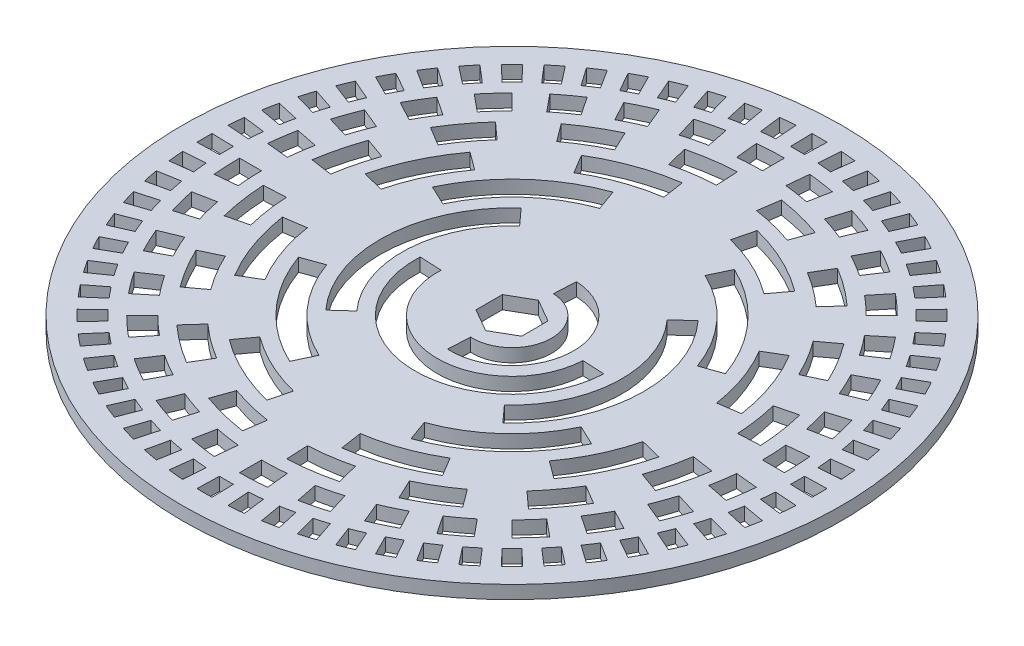
SolidWorks part; units mm, degrees
ref_plane "Front Plane" through (0, 0, 0) normal (0, 0, 1) x (1, 0, 0)
ref_plane "Top Plane" through (0, 0, 0) normal (0, 1, 0) x (1, 0, 0)
ref_plane "Right Plane" through (0, 0, 0) normal (1, 0, 0) x (0, 0, -1)
sketch "Sketch1" plane through (0, 0, 0) normal (0, 1, 0) x (1, 0, 0)
  circle A0 centre (0, 0) radius 75
  dimension "D1" = 150
extrude "Boss-Extrude1" add sketch "Sketch1" along normal blind 3
sketch "Sketch2" plane through (0, 3, 0) normal (0, 1, 0) x (1, 0, 0)
  line L0 (0, 0) -> (0, 75) construction
  line L1 (0, 0) -> (1.8406, 74.9774) construction
  line L2 (0, 0) -> (-1.8406, 74.9774) construction
  line L3 (1.7179, 69.9789) -> (1.5952, 64.9804)
  line L4 (-1.7179, 69.9789) -> (-1.5952, 64.9804)
  circle A0 centre (0, 0) radius 75 construction
  arc A1 (-1.5952, 64.9804) -> (1.5952, 64.9804) centre (0, 0) cw
  arc A2 (1.7179, 69.9789) -> (-1.7179, 69.9789) centre (0, 0) ccw
  dimension "D4" = 5
  dimension "D1" = 2.813
  dimension "D2" = 1.406
  dimension "D3" = 5
extrude "Cut-Extrude1" cut sketch "Sketch2" against normal through all
ref_axis "Axis1" through (0, 3, 0) along (0, -1, 0)
pattern_circular "CirPattern1" count 64 over 360 about axis through (0, 3, 0) along (0, -1, 0) of "Cut-Extrude1"
sketch "Sketch3" plane through (0, 3, 0) normal (0, 1, 0) x (1, 0, 0)
  line L0 (0, 0) -> (-3.6801, 74.9097) construction
  line L1 (0, 0) -> (0, 75) construction
  line L2 (0, 0) -> (-7.3513, 74.6389) construction
  line L3 (0, 0) -> (0, 75) construction
  line L4 (0, 62) -> (0, 57)
  line L5 (-5.587, 56.7255) -> (-6.0771, 61.7015)
  circle A0 centre (0, 0) radius 75 construction
  arc A1 (-6.0771, 61.7015) -> (0, 62) centre (0, 0) cw
  arc A2 (0, 57) -> (-5.587, 56.7255) centre (0, 0) ccw
  dimension "D5" = 13
  dimension "D1" = 5.625
  dimension "D2" = 2.813
  dimension "D3" = 2.813
  dimension "D4" = 5
extrude "Cut-Extrude2" cut sketch "Sketch3" against normal through all
pattern_circular "CirPattern2" count 32 over 360 about axis through (0, 3, 0) along (0, -1, 0) of "Cut-Extrude2"
sketch "Sketch5" plane through (0, 3, 0) normal (0, 1, 0) x (1, 0, 0)
  line L0 (0, 0) -> (-11.0048, 74.1882) construction
  line L1 (0, 0) -> (-3.6801, 74.9097) construction
  line L2 (0, 0) -> (-18.2235, 72.7523) construction
  line L3 (0, 0) -> (0, 75) construction
  line L4 (-2.4043, 48.941) -> (-2.6497, 53.935)
  line L5 (-11.906, 47.5315) -> (-13.1209, 52.3817)
  circle A0 centre (0, 0) radius 75 construction
  arc A1 (-13.1209, 52.3817) -> (-2.6497, 53.935) centre (0, 0) cw
  arc A2 (-2.4043, 48.941) -> (-11.906, 47.5315) centre (0, 0) ccw
  circle A4 centre (0, 0) radius 54 construction
  arc A6 (0, 62) -> (-6.0771, 61.7015) centre (0, 0) ccw construction
  dimension "D5" = 8
  dimension "D1" = 5.625
  dimension "D2" = 11.25
  dimension "D3" = 8.438
  dimension "D4" = 5
extrude "Cut-Extrude3" cut sketch "Sketch5" against normal through all
pattern_circular "CirPattern3" count 16 over 360 about axis through (0, 3, 0) along (0, -1, 0) of "Cut-Extrude3"
sketch "Sketch6" plane through (0, 3, 0) normal (0, 1, 0) x (1, 0, 0)
  line L0 (0, 0) -> (0, 75) construction
  line L1 (0, 0) -> (-11.0048, 74.1882) construction
  line L2 (0, 0) -> (-25.2667, 70.6158) construction
  line L3 (0, 0) -> (-38.5577, 64.3296) construction
  line L4 (-23.6487, 39.4555) -> (-21.0782, 35.1669)
  line L5 (-6.7496, 45.5021) -> (-6.0159, 40.5562)
  circle A0 centre (0, 0) radius 75 construction
  arc A1 (-23.6487, 39.4555) -> (-6.7496, 45.5021) centre (0, 0) cw
  arc A2 (-6.0159, 40.5562) -> (-21.0782, 35.1669) centre (0, 0) ccw
  circle A3 centre (0, 0) radius 46 construction
  arc A4 (-2.6497, 53.935) -> (-13.1209, 52.3817) centre (0, 0) ccw construction
  dimension "D5" = 8
  dimension "D1" = 22.5
  dimension "D2" = 11.25
  dimension "D3" = 19.688
  dimension "D4" = 5
extrude "Cut-Extrude4" cut sketch "Sketch6" against normal through all
pattern_circular "CirPattern4" count 8 over 360 about axis through (0, 3, 0) along (0, -1, 0) of "Cut-Extrude4"
sketch "Sketch7" plane through (0, 3, 0) normal (0, 1, 0) x (1, 0, 0)
  line L0 (0, 0) -> (0, 75) construction
  line L1 (0, 0) -> (-25.2667, 70.6158) construction
  line L2 (0, 0) -> (-67.7992, 32.0666) construction
  line L3 (0, 0) -> (-50.3669, 55.5713) construction
  line L4 (-12.8018, 35.7787) -> (-11.1174, 31.071)
  line L5 (-29.8316, 14.1093) -> (-34.3516, 16.2471)
  circle A0 centre (0, 0) radius 75 construction
  circle A1 centre (0, 0) radius 38 construction
  arc A2 (-6.7496, 45.5021) -> (-23.6487, 39.4555) centre (0, 0) ccw construction
  arc A3 (-34.3516, 16.2471) -> (-12.8018, 35.7787) centre (0, 0) cw
  arc A4 (-11.1174, 31.071) -> (-29.8316, 14.1093) centre (0, 0) ccw
  dimension "D4" = 8
  dimension "D5" = 5
  dimension "D1" = 22.5
  dimension "D2" = 45
  dimension "D3" = 42.188
extrude "Cut-Extrude5" cut sketch "Sketch7" against normal through all
pattern_circular "CirPattern5" count 4 over 360 about axis through (0, 3, 0) along (0, -1, 0) of "Cut-Extrude5"
sketch "Sketch9" plane through (0, 3, 0) normal (0, 1, 0) x (1, 0, 0)
  line L0 (0, 0) -> (0, 75) construction
  line L1 (0, 0) -> (-50.3669, 55.5713) construction
  line L2 (0, 0) -> (-55.5713, -50.3669) construction
  line L3 (0, 0) -> (-74.9097, 3.6801) construction
  line L4 (-16.789, 18.5238) -> (-20.1468, 22.2285)
  line L5 (-18.5238, -16.789) -> (-22.2285, -20.1468)
  circle A0 centre (0, 0) radius 75 construction
  circle A1 centre (0, 0) radius 30 construction
  arc A2 (-12.8018, 35.7787) -> (-34.3516, 16.2471) centre (0, 0) ccw construction
  arc A4 (-20.1468, 22.2285) -> (-22.2285, -20.1468) centre (0, 0) ccw
  arc A5 (-16.789, 18.5238) -> (-18.5238, -16.789) centre (0, 0) ccw
  dimension "D4" = 8
  dimension "D1" = 90
  dimension "D2" = 45
  dimension "D3" = 42.188
  dimension "D5" = 5
extrude "Cut-Extrude6" cut sketch "Sketch9" against normal through all
pattern_circular "CirPattern6" count 2 over 360 about axis through (0, 3, 0) along (0, -1, 0) of "Cut-Extrude6"
sketch "Sketch10" plane through (0, 3, 0) normal (0, 1, 0) x (1, 0, 0)
  line L0 (0, 0) -> (0, 75) construction
  line L1 (0, 0) -> (74.9097, -3.6801) construction
  line L2 (0, 0) -> (-74.9097, 3.6801) construction
  line L3 (0, 0) -> (-3.6801, -74.9097) construction
  line L4 (16.9795, -0.8342) -> (21.9735, -1.0795)
  line L5 (-16.9795, 0.8342) -> (-21.9735, 1.0795)
  circle A0 centre (0, 0) radius 75 construction
  circle A1 centre (0, 0) radius 22 construction
  arc A2 (20.1468, -22.2285) -> (22.2285, 20.1468) centre (0, 0) ccw construction
  arc A4 (21.9735, -1.0795) -> (-21.9735, 1.0795) centre (0, 0) cw
  arc A5 (16.9795, -0.8342) -> (-16.9795, 0.8342) centre (0, 0) cw
  dimension "D4" = 8
  dimension "D5" = 5
  dimension "D1" = 180
  dimension "D2" = 90
  dimension "D3" = 92.813
extrude "Cut-Extrude7" cut sketch "Sketch10" against normal through all
sketch "Sketch11" plane through (0, 3, 0) normal (0, 1, 0) x (1, 0, 0)
  line L0 (0, 0) -> (0, 75) construction
  line L1 (0, 0) -> (3.6801, 74.9097) construction
  line L2 (0, 0) -> (-3.6801, -74.9097) construction
  line L3 (0, 0) -> (74.9097, -3.6801) construction
  line L4 (0.4416, 8.9892) -> (0.6869, 13.9831)
  line L5 (-0.4416, -8.9892) -> (-0.6869, -13.9831)
  circle A0 centre (0, 0) radius 75 construction
  circle A1 centre (0, 0) radius 14 construction
  arc A2 (-21.9735, 1.0795) -> (21.9735, -1.0795) centre (0, 0) ccw construction
  arc A4 (0.6869, 13.9831) -> (-0.6869, -13.9831) centre (0, 0) cw
  arc A5 (0.4416, 8.9892) -> (-0.4416, -8.9892) centre (0, 0) cw
  dimension "D4" = 8
  dimension "D5" = 5
  dimension "D1" = 180
  dimension "D2" = 90
  dimension "D3" = 2.813
extrude "Cut-Extrude8" cut sketch "Sketch11" against normal through all
sketch "Sketch15" plane through (0, 3, 0) normal (0, 1, 0) x (1, 0, 0)
  line L0 (0, 0) -> (58.2029, -38.8899) construction
ref_plane "Plane1" through (54.0455, 0, 36.1121) normal (0.8315, 0, 0.5556) x (0.5556, 0, -0.8315)
sketch "Sketch18" plane through (54.0455, 0, 36.1121) normal (0.8315, 0, 0.5556) x (0.5556, 0, -0.8315)
  line L0 (0, 0) -> (0, 3.384) construction
sketch "Sketch19" plane through (0, 3, 0) normal (0, 1, 0) x (1, 0, 0)
  line L1 (5.1962, -3) -> (5.1962, 3)
  line L2 (5.1962, 3) -> (0, 6)
  line L3 (0, 6) -> (-5.1962, 3)
  line L4 (-5.1962, 3) -> (-5.1962, -3)
  line L5 (-5.1962, -3) -> (0, -6)
  line L6 (0, -6) -> (5.1962, -3)
  circle A0 centre (0, 0) radius 5.1962 construction
  dimension "D1" = 6
extrude "Cut-Extrude9" cut sketch "Sketch19" against normal through all
